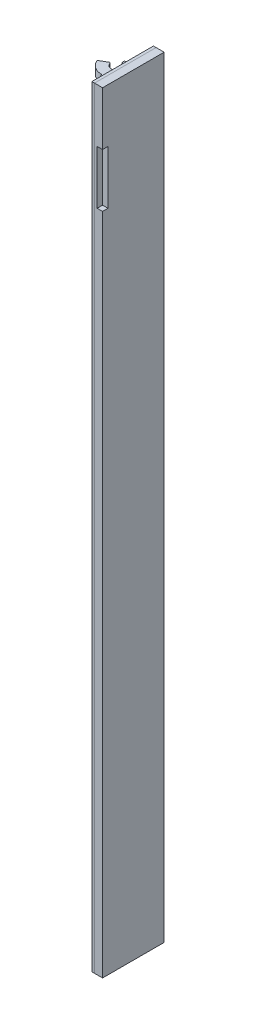
SolidWorks part; units mm, degrees
note: The reader was unsure of these and kept them because the rebuilt part matched: shared geometry of "Sketch1<2>", "Sketch3<2>", "Sketch4<2>".
ref_plane "Front Plane" through (0, 0, 0) normal (1, 0, 0) x (0, 1, 0)
ref_plane "Top Plane" through (0, 0, 0) normal (0, 0, 1) x (0, 1, 0)
ref_plane "Right Plane" through (0, 0, 0) normal (0, 1, 0) x (-1, 0, 0)
sketch "Sketch1" plane through (0, 0, 0) normal (1, 0, 0) x (0, 1, 0)
  line L1 (-144, 11.5) -> (144, 11.5)
  line L2 (-144, 11.5) -> (-144, -11.5)
  line L3 (-144, -11.5) -> (144, -11.5)
  line L4 (144, 11.5) -> (144, -11.5)
  line L5 (-144, 11.5) -> (144, -11.5) construction
  line L6 (-144, -11.5) -> (144, 11.5) construction
  point P0 (0, 0)
  dimension "D1" = 23
  dimension "D2" = 288
extrude "Boss-Extrude1" add sketch "Sketch1" along normal blind 1
extrude "Boss-Extrude5" add sketch "Sketch1<2>" along normal blind 3 from surface at 1 separate body starting at face at (1, 0, 0)
sketch "Sketch1<2>" plane through (0, 0, 0) normal (1, 0, 0) x (0, 1, 0) same geometry as "Sketch1"
sketch "Sketch2" plane through (0, 0, 0) normal (-1, 0, 0) x (0, -1, 0)
  line L1 (-136.65, 0.5) -> (-133.85, 0.5)
  line L2 (-136.65, 0.5) -> (-136.65, -11.5)
  line L3 (-136.65, -11.5) -> (-133.85, -11.5)
  line L4 (-133.85, 0.5) -> (-133.85, -11.5)
  line L5 (-135.25, 0.5) -> (-135.25, 11.5) construction
  line L6 (-144, 11.5) -> (144, 11.5) construction
  line L7 (-144, -11.5) -> (-144, 11.5) construction
  line L8 (144, -11.5) -> (-144, -11.5) construction
  line L9 (-133.85, 0.5) -> (-133.85, -11.5)
  line L10 (-136.65, 0.5) -> (-136.65, -11.5)
  line L11 (0, 2.2) -> (0, -2.2) construction
  line L12 (136.65, -11.5) -> (133.85, -11.5)
  line L13 (133.85, 0.5) -> (133.85, -11.5)
  line L14 (136.65, 0.5) -> (136.65, -11.5)
  line L15 (136.65, 0.5) -> (133.85, 0.5)
  line L16 (135.25, 0.5) -> (135.25, 11.5) construction
  line L17 (144, 11.5) -> (144, -11.5) construction
  dimension "D1" = 8.75
  dimension "D2" = 12
  dimension "D3" = 2.8
  dimension "D4" = 8.75
  dimension "D5" = 267.7
ref_plane "Plane1" through (0, 136.65, 0) normal (0, 1, 0) x (0, 0, -1)
sketch "Sketch3" plane through (0, 136.65, 0) normal (0, 1, 0) x (0, 0, -1)
  line L1 (-0.5, 0) -> (11.5, 0) construction
  line L2 (-0.5, 0) -> (11.5, 0) construction
  line L4 (5.6, 7.9) -> (4.6, 9.6321) construction
  line L5 (5.6, 7.9) -> (7.6, 7.9) construction
  line L7 (11.5, -1) -> (11.5, 0) construction
  line L8 (11.5, 0) -> (-11.5, 0) construction
  line L12 (7.8361, 7.9) -> (8.35, 7.9)
  line L13 (0, 7.9) -> (0, 7.84)
  line L14 (11.5, 0) -> (-11.5, 0) construction
  line L15 (8.6, 7.65) -> (8.6, 3.1071)
  line L16 (8.7464, 2.7536) -> (11.5, 0)
  line L17 (5.341, 10.3486) -> (3.791, 13.0332)
  line L18 (0, 0) -> (11.5, 0)
  line L19 (-0.14, 7.7) -> (-0.36, 7.7)
  line L20 (-0.5, 7.56) -> (-0.5, 4.84)
  line L21 (-0.36, 4.7) -> (-0.14, 4.7)
  line L22 (0, 4.56) -> (0, 0)
  line L23 (2.8, 12.7497) -> (3.4495, 13.1247)
  line L24 (4.6, 9.6321) -> (5.2495, 10.0071)
  arc A0 (7.5876, 7.6778) -> (4.6, 9.6321) centre (5.6, 7.9) cw
  arc A4 (0, 7.9) -> (2.8, 12.7497) centre (5.6, 7.9) cw
  arc A6 (8.35, 7.9) -> (8.6, 7.65) centre (8.35, 7.65) cw
  arc A7 (8.6, 3.1071) -> (8.7464, 2.7536) centre (9.1, 3.1071) ccw
  arc A9 (7.5876, 7.6778) -> (7.8361, 7.9) centre (7.8361, 7.65) cw
  arc A10 (-0.14, 4.7) -> (0, 4.56) centre (-0.14, 4.56) cw
  arc A11 (-0.14, 7.7) -> (0, 7.84) centre (-0.14, 7.84) ccw
  arc A12 (-0.5, 4.84) -> (-0.36, 4.7) centre (-0.36, 4.84) ccw
  arc A13 (-0.36, 7.7) -> (-0.5, 7.56) centre (-0.36, 7.56) ccw
  arc A14 (5.2495, 10.0071) -> (5.341, 10.3486) centre (5.1245, 10.2236) ccw
  arc A15 (3.4495, 13.1247) -> (3.791, 13.0332) centre (3.5745, 12.9082) cw
  point P0 (11.5, 0)
  point P1 (5.1972, 10.1668)
  point P16 (2.8, 12.7497)
  point P22 (3.2487, 13.0558)
  point P26 (8.6, 7.9)
  point P30 (4.6791, 9.5102)
  point P41 (0, 4.7)
  point P44 (0, 7.7)
  point P47 (-0.5, 4.7)
  point P50 (-0.5, 7.7)
  point P51 (0, 0)
  point P53 (0, 0)
  point P58 (3.666, 13.2497)
  point P59 (0, 0)
  point P60 (0, 0)
  point P61 (4.6, 9.5376)
  dimension "D1" = 3.9
  dimension "D2" = 5.9
  dimension "D3" = 2
  dimension "D4" = 120
  dimension "D6" = 11.5
  dimension "D7" = 5.6
  dimension "D8" = 45
  dimension "D9" = 1
  dimension "D10" = 1
  dimension "D11" = 0.25
  dimension "D12" = 0.5
  dimension "D15" = 0.14
  dimension "D16" = 0.5
  dimension "D5" = 2
  dimension "D13" = 3
  dimension "D14" = 4.7
extrude "Boss-Extrude2" add sketch "Sketch3" against normal up to vertex (2.8 mm away) up to point (0, 133.85, -11.5)
extrude "Boss-Extrude3" add sketch "Sketch3<2>" against normal up to vertex (273.3 mm away) from vertex at -270.5 starting at point (0, -133.85, -11.5)
sketch "Sketch3<2>" plane through (0, 136.65, 0) normal (0, 1, 0) x (0, 0, -1) same geometry as "Sketch3"
sketch "Sketch4" plane through (4, 0, 0) normal (1, 0, 0) x (0, 1, 0)
  line L6 (105.8946, 6.8232) -> (108.3946, 4.3232)
  line L7 (108.3946, 4.3232) -> (110.8946, 6.8232)
  line L8 (110.8946, 6.8232) -> (105.8946, 6.8232)
  line L13 (-30, -5) -> (-29, -5)
  line L14 (-29, -5) -> (-29, -0.5)
  line L15 (-29, -0.5) -> (-10, -0.5)
  line L16 (-10, -0.5) -> (-10, 5)
  line L17 (-10, 5) -> (-30, 5)
  line L19 (-30, 0.5) -> (-11, 0.5)
  line L20 (-11, 0.5) -> (-11, 4)
  line L21 (-11, 4) -> (-30, 4)
  line L22 (10, 5) -> (10, 4)
  line L23 (10, 4) -> (0.5, 4)
  line L24 (0.5, 4) -> (0.5, -5)
  line L27 (0.5, -5) -> (-10, -5)
  line L28 (10, 5) -> (-0.5, 5)
  line L29 (-0.5, 5) -> (-0.5, -4)
  line L32 (-0.5, -4) -> (-10, -4)
  line L33 (-10, -4) -> (-10, -5)
  line L34 (29.9456, 5) -> (32, 5)
  line L35 (32, 5) -> (23.0272, 0)
  line L36 (23.0272, 0) -> (32, -5)
  line L37 (32, -5) -> (29.9456, -5)
  line L38 (29.9456, -5) -> (22, -0.5724)
  line L39 (22, -0.5724) -> (14.0544, -5)
  line L40 (14.0544, -5) -> (12, -5)
  line L41 (12, -5) -> (20.9728, 0)
  line L42 (20.9728, 0) -> (12, 5)
  line L43 (12, 5) -> (14.0544, 5)
  line L44 (14.0544, 5) -> (22, 0.5724)
  line L45 (22, 0.5724) -> (29.9456, 5)
  line L46 (32, 5) -> (12, 5) construction
  line L47 (10, 5) -> (-10, 5) construction
  line L48 (0.5, -5) -> (-0.5, -4) construction
  line L49 (22, -0.5724) -> (22, 0.5724) construction
  line L50 (23.0272, 0) -> (20.9728, 0) construction
  line L51 (0.5, 4) -> (-0.5, 5) construction
  line L52 (12, 5) -> (12, -5) construction
  line L53 (32, 5) -> (32, -5) construction
  line L54 (-30, 5) -> (-30, 4)
  line L55 (-30, 0.5) -> (-30, -5)
  line L56 (-11, 0.5) -> (-10, -0.5) construction
  line L57 (-11, 4) -> (-10, 5) construction
  line L58 (-30, 0.5) -> (-29, -0.5) construction
  line L59 (-10, 5) -> (-10, -5) construction
  line L60 (-30, -5) -> (-10, -5) construction
  line L61 (-10, -5) -> (-10, 5) construction
  line L62 (-30, 0) -> (-10, 0) construction
  line L63 (-10, 0) -> (10, 0) construction
  line L64 (14.0544, -5) -> (13.5676, -4.1265) construction
  line L66 (12, 5) -> (10, 5) construction
  text T0 "OPEN" font "Arial" height 2.5
  point P29 (-10.5, 0)
  dimension "D2" = 2
  dimension "D4" = 2.5
  dimension "D5" = 4
  dimension "D6" = 1
  dimension "D7" = 1
  dimension "D9" = 10
  dimension "D10" = 20
extrude "Cut-Extrude1" cut sketch "Sketch4" along normal blind 1 from vertex at -3 starting at point (1, 144, 11.5)
extrude "Boss-Extrude4" add sketch "Sketch4<2>" along normal blind 1 from vertex at -3 separate body
sketch "Sketch4<2>" plane through (4, 0, 0) normal (1, 0, 0) x (0, 1, 0) same geometry as "Sketch4"
sketch "Sketch6" plane through (4, 0, 0) normal (1, 0, 0) x (0, 1, 0)
  line L0 (-144, 11.5) -> (144, 11.5) construction
  line L1 (124, 11.5) -> (104, 11.5)
  line L2 (124, 11.5) -> (124, 9.5)
  line L3 (124, 9.5) -> (104, 9.5)
  line L4 (104, 11.5) -> (104, 9.5)
  line L5 (144, 11.5) -> (144, -11.5) construction
  dimension "D1" = 20
  dimension "D2" = 20
  dimension "D3" = 2
extrude "Cut-Extrude2" cut sketch "Sketch6" against normal blind 2
